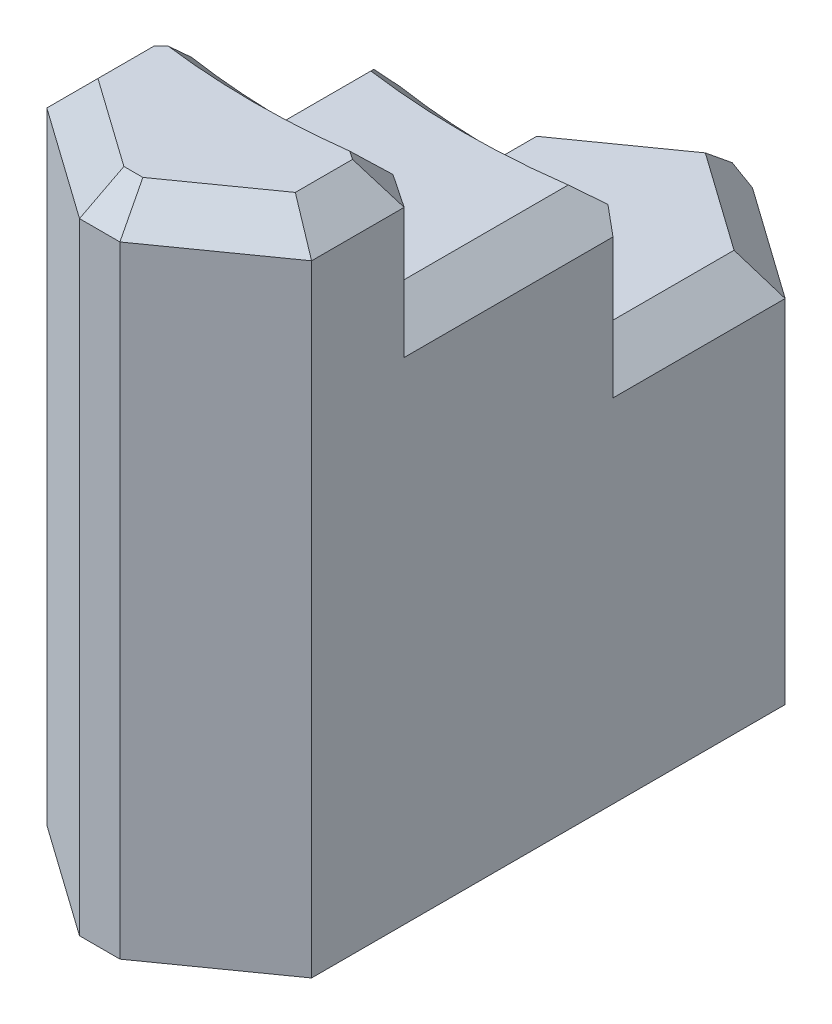
SolidWorks part; units mm, degrees
ref_plane "Front Plane" through (0, 0, 0) normal (0, 0, 1) x (1, 0, 0)
ref_plane "Top Plane" through (0, 0, 0) normal (0, 1, 0) x (1, 0, 0)
ref_plane "Right Plane" through (0, 0, 0) normal (1, 0, 0) x (0, 0, -1)
sketch "Sketch1" plane through (0, 0, 0) normal (1, 0, 0) x (0, 0, -1)
  line L0 (7.5692, 24.6888) -> (7.5692, 19.7866)
  line L1 (0, 0) -> (23.8506, 0)
  line L2 (0, 0) -> (0, 24.6888)
  line L3 (0, 24.6888) -> (7.5692, 24.6888)
  line L4 (23.8506, 0) -> (23.8506, 14.5288)
  line L5 (7.5692, 19.7866) -> (15.4432, 19.7866)
  line L6 (15.4432, 19.7866) -> (15.4432, 14.5288)
  line L7 (15.4432, 14.5288) -> (23.8506, 14.5288)
  dimension "D1" = 24.6888
  dimension "D2" = 23.8506
  dimension "D3" = 7.5692
  dimension "D4" = 15.4432
  dimension "D5" = 14.5288
  dimension "D6" = 19.7866
extrude "Extrude1" add sketch "Sketch1" along normal blind 9.9822
sketch "Sketch2" plane through (0, 24.6888, 0) normal (0, 1, 0) x (1, 0, 0)
  line L0 (0, 7.5692) -> (0, 2.9972) construction
  line L1 (0, 7.5692) -> (0, 0) construction
  line L2 (0, 2.9972) -> (4.2291, 0)
  line L3 (9.9822, 0) -> (0, 0) construction
  line L4 (4.2291, 0) -> (4.9911, 0) construction
  line L5 (4.9911, 0) -> (4.9911, 7.5692) construction
  line L6 (9.9822, 7.5692) -> (0, 7.5692) construction
  line L7 (0, 2.9972) -> (0, 0)
  line L8 (0, 0) -> (4.2291, 0)
  line L9 (9.9822, 2.9972) -> (9.9822, 0)
  line L10 (9.9822, 0) -> (5.7531, 0)
  line L11 (9.9822, 2.9972) -> (5.7531, 0)
  line L12 (0, 23.8506) -> (4.2291, 23.8506)
  line L13 (9.9822, 23.8506) -> (0, 23.8506) construction
  line L14 (4.2291, 23.8506) -> (0, 20.8534)
  line L15 (0, 23.8506) -> (0, 15.4432) construction
  line L16 (0, 20.8534) -> (0, 23.8506)
  line L17 (4.9911, 23.8506) -> (4.9911, 7.5692) construction
  line L19 (9.9822, 20.8534) -> (9.9822, 23.8506)
  line L20 (9.9822, 23.8506) -> (5.7531, 23.8506)
  line L21 (4.2291, 23.8506) -> (4.9911, 23.8506) construction
  line L22 (5.7531, 23.8506) -> (9.9822, 20.8534)
  dimension "D1" = 4.572
  dimension "D2" = 0.762
  dimension "D3" = 0.762
extrude "Cut-Extrude1" cut sketch "Sketch2" against normal through all
sketch "Sketch3" plane through (0, 24.6888, 0) normal (0, 1, 0) x (1, 0, 0)
  line L0 (4.9911, 7.5692) -> (4.9911, 32.9692) construction
  line L1 (9.9822, 7.5692) -> (0, 7.5692) construction
  circle A0 centre (4.9911, 32.9692) radius 25.8857
  dimension "D1" = 25.4
extrude "Cut-Extrude2" cut sketch "Sketch3" against normal up to surface (4.9022 mm away) up to face at (4.9911, 19.7866, -11.5062)
sketch "Sketch4" plane through (0, 19.7866, 0) normal (0, 1, 0) x (1, 0, 0)
  line L0 (4.9911, 15.4432) -> (4.9911, 40.8432) construction
  line L1 (9.9822, 15.4432) -> (0, 15.4432) construction
  circle A0 centre (4.9911, 40.8432) radius 25.8857
  dimension "D1" = 25.4
extrude "Cut-Extrude3" cut sketch "Sketch4" against normal up to surface (5.2578 mm away) up to face at (4.9911, 14.5288, -20.0491)
chamfer "Chamfer1" distance 1.27 angle 45 4 edges at (0, 17.1577, -15.4432) (9.9822, 17.1577, -15.4432) (9.9822, 22.2377, -7.5692) (0, 22.2377, -7.5692) first distance on face at (0, 14.751, -11.7157) first distance on face at (4.9911, 17.1577, -15.2003) first distance on face at (4.9911, 22.2377, -7.3263)
chamfer "Chamfer2" distance 1.27 angle 45 12 edges at (7.8677, 24.6888, -1.4986) (4.9911, 24.6888, 0) (2.1146, 24.6888, -1.4986) (0, 24.6888, -4.6482) (0.5406, 24.6888, -6.8398) (4.8883, 24.6888, -7.0837) (9.3399, 24.6888, -6.9188) (9.9822, 24.6888, -4.7423) (9.9822, 14.5288, -17.6074) (0, 14.5288, -17.5133) (0, 19.7866, -10.2362) (9.9822, 19.7866, -10.4245)
chamfer "Chamfer3" distance 1.27 angle 45 2 edges at (7.2326, 14.5288, -22.802) (4.9837, 19.7866, -14.9575)
chamfer "Chamfer4" distance 1.27 angle 45 1 edges at (2.5815, 14.5288, -22.6829)
